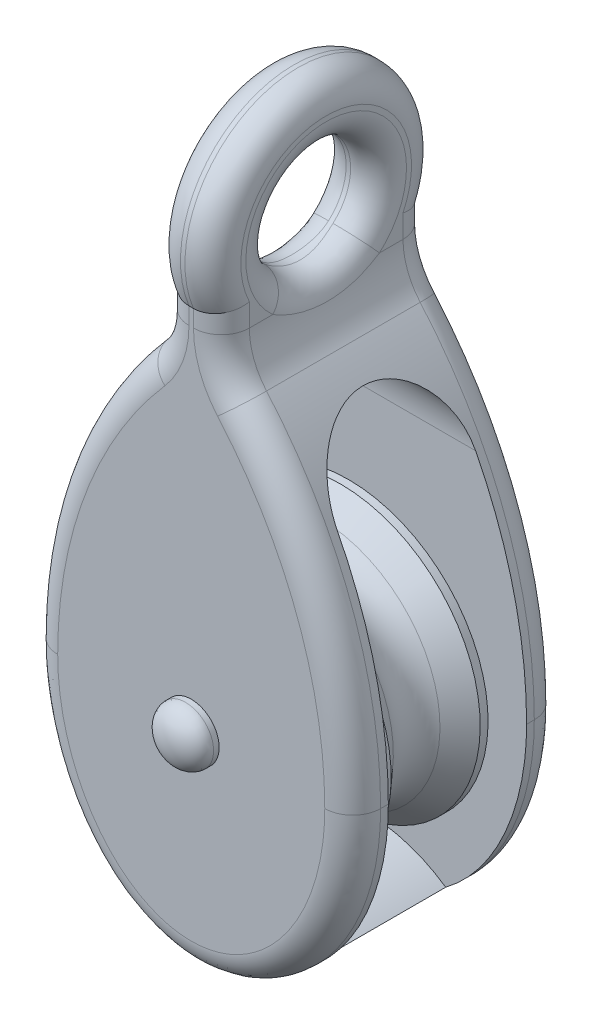
SolidWorks part; units mm, degrees
ref_plane "Front Plane" through (0, 0, 0) normal (0, 0, 1) x (1, 0, 0)
ref_plane "Top Plane" through (0, 0, 0) normal (0, 1, 0) x (1, 0, 0)
ref_plane "Right Plane" through (0, 0, 0) normal (1, 0, 0) x (0, 0, -1)
sketch "Sketch1" plane through (0, 0, 0) normal (1, 0, 0) x (0, 0, -1)
  line L0 (-4.0481, 12.7) -> (-2.1194, 10.9709)
  line L1 (-4.7625, 12.7) -> (-4.0481, 12.7)
  line L2 (-4.7625, 12.7) -> (-4.7625, 0)
  line L3 (-4.7625, 0) -> (-9.2704, 0) construction
  line L4 (4.7625, 12.7) -> (4.7625, 0)
  line L5 (2.1194, 10.9709) -> (4.0481, 12.7)
  line L6 (4.0481, 12.7) -> (4.7625, 12.7)
  line L7 (4.7625, 0) -> (-4.7625, 0) construction
  line L8 (-4.7625, 0) -> (4.7625, 0)
  arc A0 (-2.1194, 10.9709) -> (2.1194, 10.9709) centre (0, 13.335) ccw
  circle A1 centre (0, 13.335) radius 3.175 construction
  circle A2 centre (0, -13.335) radius 3.175 construction
  dimension "D3" = 0.7144
  dimension "Rope Dia" = 6.35
  dimension "D2" = 20.32
  dimension "pulley width" = 9.525
  dimension "Pulley OD" = 25.4
revolve "Revolve1" add sketch "Sketch1" angle 360 about L3
sketch "Sketch2" plane through (0, 0, 0) normal (0, 0, 1) x (1, 0, 0)
  line L0 (0, 32.5628) -> (0, -19.05) construction
  line L1 (-14.6812, 0) -> (14.6812, 0) construction
  line L9 (-2.7432, 29.3878) -> (2.7432, 29.3878) construction
  line L10 (-2.7432, 47.625) -> (2.7432, 47.625)
  line L11 (-2.7432, 47.625) -> (-2.7432, 29.3878)
  line L12 (2.7432, 29.3878) -> (2.7432, 47.625)
  arc A0 (14.6812, 0) -> (2.7432, 29.3878) centre (-27.4598, 0) ccw
  arc A1 (-2.7432, 29.3878) -> (-14.6812, 0) centre (27.4598, 0) ccw
  circle A2 centre (0, 0) radius 12.7 construction
  circle A3 centre (0, 0) radius 12.7
  circle A4 centre (0, 37.3253) radius 4.7625
  ellipse E0 centre (0, 0) end of major axis (0, -19.05) minor radius 14.6812
  point P2 (0, 29.3878)
  point P27 (0, 47.625)
  point P28 (0, 42.0878)
  dimension "opening" = 9.525
  dimension "D2" = 3.175
  dimension "Center to base" = 19.05
  dimension "Height" = 66.675
  dimension "width" = 29.3624
  dimension "ring dia" = 5.5372
  dimension "ring width" = 5.4864
sketch "Sketch3" plane through (0, 0, 0) normal (0, 0, 1) x (1, 0, 0)
  line L0 (-2.7432, 29.3878) -> (2.7432, 29.3878) construction
  line L1 (-2.7432, 47.625) -> (2.7432, 47.625) construction
  line L2 (-2.7432, 47.625) -> (-2.7432, 29.3878) construction
  line L3 (2.7432, 29.3878) -> (2.7432, 47.625) construction
  line L4 (-2.7432, 47.625) -> (2.7432, 47.625)
  line L5 (-2.7432, 47.625) -> (-2.7432, 29.3878)
  line L6 (2.7432, 29.3878) -> (2.7432, 47.625)
  arc A0 (-2.7432, 29.3878) -> (-14.6812, 0) centre (27.4598, 0) ccw construction
  arc A1 (14.6812, 0) -> (2.7432, 29.3878) centre (-27.4598, 0) ccw construction
  arc A2 (-2.7432, 29.3878) -> (-14.6812, 0) centre (27.4598, 0) ccw
  arc A3 (14.6812, 0) -> (2.7432, 29.3878) centre (-27.4598, 0) ccw
  ellipse E0 centre (0, 0) end of major axis (0, -19.05) minor radius 14.6812 construction
  ellipse E1 centre (0, 0) end of major axis (0, -19.05) minor radius 14.6812 (-14.6812, 0) -> (14.6812, 0) ccw
extrude "Boss-Extrude1" add sketch "Sketch3" along normal mid plane 19.05 separate body
sketch "Sketch4" plane through (0, 0, 0) normal (1, 0, 0) x (0, 0, -1)
  line L0 (0, 0) -> (0, 19.2151) construction
  line L1 (-6.2865, 19.2151) -> (6.2865, 19.2151) construction
  line L2 (-6.2865, 19.2151) -> (-6.2865, -13.335)
  line L3 (-6.2865, -13.335) -> (6.2865, -13.335)
  line L4 (6.2865, 19.2151) -> (6.2865, -13.335)
  line L5 (-9.525, 29.3878) -> (9.525, 29.3878) construction
  line L8 (4.7625, 12.7) -> (4.7625, 0) construction
  line L9 (6.2865, 19.2151) -> (9.525, 19.2151) construction
  line L10 (9.525, 0) -> (9.525, 29.3878) construction
  line L11 (0, 29.3878) -> (0, 25.5016) construction
  arc A0 (-6.2865, 19.2151) -> (6.2865, 19.2151) centre (0, 19.2151) cw
  circle A1 centre (0, 37.3253) radius 4.7625
  dimension "D1" = 1.524
  dimension "D3" = 3.2385
  dimension "D4" = 3.8862
extrude "Cut-Extrude1" cut sketch "Sketch4" against normal blind 76.2 and the other way blind 76.2
sketch "Sketch20" plane through (0, 0, 0) normal (1, 0, 0) x (0, 0, -1)
  circle A0 centre (0, 37.3253) radius 10.2997
  circle A1 centre (0, 37.3253) radius 4.7625 construction
  circle A2 centre (0, 37.3253) radius 4.7625
extrude "Boss-Extrude5" add sketch "Sketch20" along normal up to vertex (2.7432 mm away) and the other way up to vertex (2.7432 mm away) up to point (2.7432, 47.625, 0) other way up to point (-2.7432, 47.625, 0)
sketch "Sketch21" plane through (-2.7432, 0, 0) normal (-1, 0, 0) x (0, 0, 1)
  line L0 (-10.2997, 37.3253) -> (-12.8397, 37.3253)
  line L1 (-12.8397, 37.3253) -> (-12.8397, 50.165)
  line L2 (-12.8397, 50.165) -> (12.8397, 50.165)
  line L3 (12.8397, 50.165) -> (12.8397, 37.3253)
  line L4 (10.2997, 37.3253) -> (12.8397, 37.3253)
  line L5 (9.525, 47.625) -> (-9.525, 47.625) construction
  arc A0 (10.2997, 37.3253) -> (-10.2997, 37.3253) centre (0, 37.3253) ccw
  dimension "D1" = 2.54
  dimension "D2" = 2.54
extrude "Cut-Extrude3" cut sketch "Sketch21" against normal through all
sketch "Sketch6" plane through (0, 0, 0) normal (0, 0, 1) x (1, 0, 0)
  line L0 (0, 32.5628) -> (0, -19.05) construction
  line L2 (10.4845, -13.335) -> (-10.4845, -13.335) construction
  line L3 (0, -14.224) -> (0, -13.335) construction
  line L5 (-10.4845, -13.335) -> (10.4845, -13.335)
  arc A0 (-7.3243, -16.51) -> (7.3243, -16.51) centre (0, -27.1004) cw
  circle A1 centre (0, 0) radius 12.7 construction
  circle A2 centre (0, 0) radius 12.7 construction
  ellipse E0 centre (0, 0) end of major axis (0, -19.05) minor radius 14.6812 construction
  ellipse E1 centre (0, 0) end of major axis (0, -19.05) minor radius 14.6812 (-10.4845, -13.335) -> (-7.3243, -16.51) ccw
  ellipse E2 centre (0, 0) end of major axis (0, -19.05) minor radius 14.6812 (7.3243, -16.51) -> (10.4845, -13.335) ccw
  point P27 (0, -12.7)
  dimension "D2" = 3.175
  dimension "D1" = 1.524
extrude "Cut-Extrude2" cut sketch "Sketch6" against normal up to surface and the other way up to surface up to face at (0, 1.8737, -6.2865) other way up to face at (0, 1.8737, 6.2865)
fillet "Fillet3" radius 6.35 2 edges at (-2.7432, 29.3878, 0) (2.7432, 29.3878, 0)
fillet "Fillet2" radius 2.54 18 edges at (-12.0024, 14.7851, -9.525) (0, -19.05, -9.525) (-12.0024, 14.7851, 9.525) (0, -19.05, 9.525) (12.0024, 14.7851, -9.525) (12.0024, 14.7851, 9.525) (2.7432, 32.5628, 0) (-2.7432, 42.0878, 0) (-2.7432, 32.6347, -9.525) (2.7432, 32.6347, 9.525) (2.7432, 32.6347, -9.525) (-2.7432, 32.6347, 9.525) (-2.7432, 47.625, 0) (2.7432, 47.625, 0) (-3.1469, 29.6352, -9.525) (3.1469, 29.6352, -9.525) (-3.1469, 29.6352, 9.525) (3.1469, 29.6352, 9.525)
sketch "Sketch7" plane through (0, 0, -9.525) normal (0, 0, -1) x (-1, 0, 0)
  circle A0 centre (0, 0) radius 2.54
  dimension "D1" = 5.08
extrude "Boss-Extrude2" add sketch "Sketch7" along normal blind 0.508
dome "Dome1" faces to dome 1 distance 1.6933 reverse direction no elliptical dome yes face at (-2.54, 0, -10.033) parameters "D1"=1.6933
mirror "Mirror1" about plane through (0, 0, 0) normal (0, 0, 1) of "Boss-Extrude2", "Dome1"
sketch "Sketch8" plane through (0, 0, -6.2865) normal (0, 0, 1) x (1, 0, 0)
  circle A0 centre (0, 0) radius 1.905
  dimension "D1" = 3.81
extrude "Boss-Extrude3" add sketch "Sketch8" along normal up to surface (12.573 mm away) up to face at (0, 0.9477, 6.2865)
equation "\"D3@Sketch1\" = \"pulley width@Sketch1\"*.075"
equation "\"D2@Sketch1\" = \"Pulley OD@Sketch1\"*.80"
equation "\"D4@Sketch4\" = \"D3@Sketch4\"*1.2"
equation "\"D2@Sketch2\" = \"opening@Sketch2\"/3"
equation "\"D1@Sketch7\" = \"Pulley OD@Sketch1\"*.2"
equation "\"D1@Dome1\" = \"D1@Sketch7\"/3"
equation "\"D1@Boss-Extrude2\" = \"D1@Sketch7\"*.1"
equation "\"D1@Sketch8\" = \"D1@Sketch7\"*.750"
